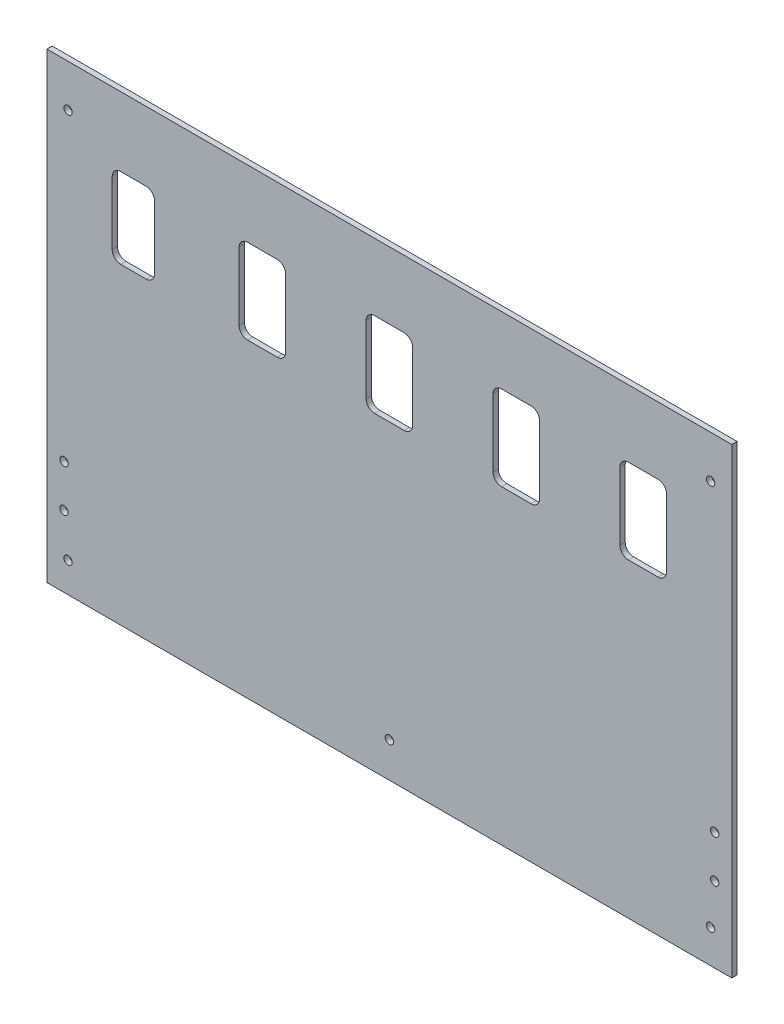
SolidWorks part; units mm, degrees
material "ABS PC"
ref_plane "Front Plane" through (0, 0, 0) normal (0, 0, 1) x (1, 0, 0)
ref_plane "Top Plane" through (0, 0, 0) normal (0, 1, 0) x (1, 0, 0)
ref_plane "Right Plane" through (0, 0, 0) normal (1, 0, 0) x (0, 0, -1)
sketch "Sketch1" plane through (0, 0, 0) normal (0, 0, 1) x (1, 0, 0)
  line L1 (-205.5812, -138.684) -> (205.5812, -138.684)
  line L2 (-205.5812, -138.684) -> (-205.5812, 138.684)
  line L3 (-205.5812, 138.684) -> (205.5812, 138.684)
  line L4 (205.5812, -138.684) -> (205.5812, 138.684)
  line L5 (0, 138.684) -> (0, -138.684) construction
  line L6 (-205.5812, 0) -> (205.5813, 0) construction
  point P0 (0, 0)
  point P4 (-137.0013, 0)
  point P5 (137.0013, 0)
  point P6 (0, 97.0788)
  point P7 (0, -97.0788)
  dimension "Width" = 277.368
  dimension "Break" = 68.58
  dimension "D2" = 68.58
  dimension "D1" = 41.6052
  dimension "D3" = 41.6052
  dimension "D4" = 411.1625
sketch "Sketch2" plane through (0, 0, 0) normal (1, 0, 0) x (0, 0, -1)
  line L0 (-1.5875, -138.684) -> (1.5875, -138.684)
  dimension "Thickness" = 3.175
sketch "Sketch3" plane through (0, 0, 0) normal (0, 0, 1) x (1, 0, 0)
  line L0 (-205.5812, -138.684) -> (-205.5812, 138.684) construction
  line L1 (-205.5812, -138.684) -> (205.5812, -138.684) construction
  line L2 (205.5812, -138.684) -> (205.5812, 138.684) construction
  line L3 (-205.5812, 138.684) -> (205.5812, 138.684) construction
  line L4 (-205.5812, -138.684) -> (-205.5812, 138.684)
  line L5 (-205.5812, -138.684) -> (205.5812, -138.684)
  line L6 (205.5812, -138.684) -> (205.5812, 138.684)
  line L7 (-205.5812, 138.684) -> (205.5812, 138.684)
extrude "Boss-Extrude1" add sketch "Sketch3" along normal mid plane 3.175
sketch "Sketch4" plane through (0, 0, 1.5875) normal (0, 0, 1) x (1, 0, 0)
  line L0 (-227.6475, 73.0327) -> (-161.29, 73.0327) construction
  line L1 (-82.55, 73.0327) -> (-82.55, 98.4327) construction
  line L2 (-82.55, 98.4327) -> (-90.17, 98.4327) construction
  line L3 (-161.29, 73.0327) -> (-161.29, 97.1627) construction
  line L6 (-227.6475, -105.791) -> (-227.6475, 52.959) construction
  line L7 (-227.6475, -115.316) -> (-227.6475, 138.684) construction
  line L8 (-161.29, 73.0327) -> (-82.55, 73.0327) construction
  line L9 (-82.55, 73.0327) -> (-6.35, 73.0327) construction
  line L10 (-6.35, 73.0327) -> (69.85, 73.0327) construction
  line L11 (69.85, 73.0327) -> (146.05, 73.0327) construction
  line L12 (-82.55, 73.0327) -> (-82.55, 47.6327) construction
  line L13 (-82.55, 47.6327) -> (-62.23, 47.6327) construction
  line L16 (-161.29, 97.1627) -> (-166.37, 97.1627) construction
  line L17 (-161.29, 73.0327) -> (-161.29, 48.9027) construction
  line L18 (-161.29, 48.9027) -> (-140.97, 48.9027) construction
  line L19 (-6.35, 73.0327) -> (-6.35, 98.4327) construction
  line L24 (-6.35, 98.4327) -> (-13.97, 98.4327) construction
  line L25 (-6.35, 73.0327) -> (-6.35, 47.6327) construction
  line L26 (-6.35, 47.6327) -> (13.97, 47.6327) construction
  line L27 (69.85, 73.0327) -> (69.85, 98.4327) construction
  line L28 (-8.89, 98.4327) -> (8.89, 98.4327)
  line L29 (-13.97, 93.3527) -> (-13.97, 52.7127)
  line L30 (-8.89, 47.6327) -> (8.89, 47.6327)
  line L31 (13.97, 93.3527) -> (13.97, 52.7127)
  line L32 (69.85, 98.4327) -> (62.23, 98.4327) construction
  line L33 (69.85, 73.0327) -> (69.85, 47.6327) construction
  line L34 (69.85, 47.6327) -> (90.17, 47.6327) construction
  line L35 (146.05, 73.0327) -> (146.05, 98.4327) construction
  line L36 (67.31, 98.4327) -> (85.09, 98.4327)
  line L37 (62.23, 93.3527) -> (62.23, 52.7127)
  line L38 (67.31, 47.6327) -> (85.09, 47.6327)
  line L39 (90.17, 93.3527) -> (90.17, 52.7127)
  line L40 (146.05, 98.4327) -> (138.43, 98.4327) construction
  line L41 (146.05, 73.0327) -> (146.05, 47.6327) construction
  line L42 (146.05, 47.6327) -> (166.37, 47.6327) construction
  line L43 (-205.5812, 138.684) -> (-205.5812, 73.0327) construction
  line L44 (143.51, 98.4327) -> (161.29, 98.4327)
  line L45 (138.43, 93.3527) -> (138.43, 52.7127)
  line L46 (143.51, 47.6327) -> (161.29, 47.6327)
  line L47 (166.37, 93.3527) -> (166.37, 52.7127)
  line L48 (-85.09, 98.4327) -> (-67.31, 98.4327)
  line L49 (-90.17, 93.3527) -> (-90.17, 52.7127)
  line L50 (-85.09, 47.6327) -> (-67.31, 47.6327)
  line L51 (-62.23, 93.3527) -> (-62.23, 52.7127)
  line L53 (-161.29, 97.1627) -> (-146.05, 97.1627)
  line L54 (-166.37, 92.0827) -> (-166.37, 53.9827)
  line L55 (-161.29, 48.9027) -> (-146.05, 48.9027)
  line L56 (-140.97, 92.0827) -> (-140.97, 53.9827)
  arc A0 (138.43, 52.7127) -> (143.51, 47.6327) centre (143.51, 52.7127) ccw
  arc A1 (166.37, 52.7127) -> (161.29, 47.6327) centre (161.29, 52.7127) cw
  arc A2 (161.29, 98.4327) -> (166.37, 93.3527) centre (161.29, 93.3527) cw
  arc A3 (138.43, 93.3527) -> (143.51, 98.4327) centre (143.51, 93.3527) cw
  arc A4 (62.23, 52.7127) -> (67.31, 47.6327) centre (67.31, 52.7127) ccw
  arc A5 (90.17, 52.7127) -> (85.09, 47.6327) centre (85.09, 52.7127) cw
  arc A6 (85.09, 98.4327) -> (90.17, 93.3527) centre (85.09, 93.3527) cw
  arc A7 (67.31, 98.4327) -> (62.23, 93.3527) centre (67.31, 93.3527) ccw
  arc A8 (-13.97, 52.7127) -> (-8.89, 47.6327) centre (-8.89, 52.7127) ccw
  arc A9 (13.97, 52.7127) -> (8.89, 47.6327) centre (8.89, 52.7127) cw
  arc A10 (8.89, 98.4327) -> (13.97, 93.3527) centre (8.89, 93.3527) cw
  arc A11 (-8.89, 98.4327) -> (-13.97, 93.3527) centre (-8.89, 93.3527) ccw
  arc A19 (-90.17, 52.7127) -> (-85.09, 47.6327) centre (-85.09, 52.7127) ccw
  arc A20 (-62.23, 52.7127) -> (-67.31, 47.6327) centre (-67.31, 52.7127) cw
  arc A21 (-67.31, 98.4327) -> (-62.23, 93.3527) centre (-67.31, 93.3527) cw
  arc A22 (-85.09, 98.4327) -> (-90.17, 93.3527) centre (-85.09, 93.3527) ccw
  arc A23 (-166.37, 53.9827) -> (-161.29, 48.9027) centre (-161.29, 53.9827) ccw
  arc A24 (-146.05, 48.9027) -> (-140.97, 53.9827) centre (-146.05, 53.9827) ccw
  arc A25 (-146.05, 97.1627) -> (-140.97, 92.0827) centre (-146.05, 92.0827) cw
  arc A26 (-161.29, 97.1627) -> (-166.37, 92.0827) centre (-161.29, 92.0827) ccw
  point P16 (-76.2, 98.4327)
  point P17 (-90.17, 73.0327)
  point P18 (-13.97, 73.0327)
  point P95 (62.23, 73.0327)
  point P96 (138.43, 73.0327)
  point P97 (0, 98.4327)
  point P98 (76.2, 98.4327)
  point P99 (152.4, 98.4327)
  dimension "D1" = 5.08
  dimension "D2" = 5.08
  dimension "D5" = 5.08
  dimension "D9" = 27.94
  dimension "D10" = 27.94
  dimension "D11" = 27.94
  dimension "D12" = 27.94
  dimension "D3" = 76.2
  dimension "D4" = 76.2
  dimension "D6" = 152.4
  dimension "D7" = 65.6513
extrude "Cut-Extrude1" cut sketch "Sketch4" against normal blind 25.4 contours L53 A26 L54 A23 L55 A24 L56 A25 | A22 L48 A21 L51 A20 L50 A19 L49 | L29 A8 L30 A9 L31 A10 L28 A11 | L37 A4 L38 A5 L39 A6 L36 A7 | A3 L44 A2 L47 A1 L46 A0 L45 region at (-153.67, 73.0327, 1.5875)
hole_wizard "#10 Clearance Hole1" positions "Sketch5" profile "Sketch6" hole size "#10" standard "ANSI Inch" end condition through all
sketch "Sketch5" plane through (0, 0, 1.5875) normal (0, 0, 1) x (1, 0, 0)
  point P6 (192.8812, 113.284)
  point P8 (-192.8812, -120.7642)
  point P10 (192.8812, -118.6475)
  point P12 (-192.8812, 113.284)
sketch "Sketch6" plane through (192.8812, 113.284, 1.5875) normal (1, 0, 0) x (0, -1, 0)
  line L0 (0, 0) -> (0, 3.175)
  line L1 (0, 3.175) -> (2.4892, 3.175)
  line L2 (2.4892, 3.175) -> (2.4892, 0)
  line L5 (2.4892, 0) -> (0, 0)
  line L11 (0, -6.35) -> (0, 107.95) construction
  dimension "Thru Hole Dia." = 4.9784
  dimension "Thru Hole Depth" = 3.175
hole_wizard "#10 Clearance Hole2" positions "Sketch7" profile "Sketch8" hole size "#10" standard "ANSI Inch" end condition through all
sketch "Sketch7" plane through (0, 0, 1.5875) normal (0, 0, 1) x (1, 0, 0)
  point P0 (0, -117.5325)
sketch "Sketch8" plane through (0, -117.5325, 1.5875) normal (1, 0, 0) x (0, -1, 0)
  line L0 (0, 0) -> (0, 3.175)
  line L1 (0, 3.175) -> (2.4892, 3.175)
  line L2 (2.4892, 3.175) -> (2.4892, 0)
  line L5 (2.4892, 0) -> (0, 0)
  line L11 (0, -6.35) -> (0, 107.95) construction
  dimension "Thru Hole Dia." = 4.9784
  dimension "Thru Hole Depth" = 3.175
hole_wizard "#10 Clearance Hole3" positions "Sketch9" profile "Sketch10" hole size "#10" standard "ANSI Inch" end condition through all
sketch "Sketch9" plane through (0, 0, 1.5875) normal (0, 0, 1) x (1, 0, 0)
  point P0 (-195.3063, -70.6157)
sketch "Sketch10" plane through (-195.3063, -70.6157, 1.5875) normal (1, 0, 0) x (0, -1, 0)
  line L0 (0, 0) -> (0, 3.175)
  line L1 (0, 3.175) -> (2.4892, 3.175)
  line L2 (2.4892, 3.175) -> (2.4892, 0)
  line L5 (2.4892, 0) -> (0, 0)
  line L11 (0, -6.35) -> (0, 107.95) construction
  dimension "Thru Hole Dia." = 4.9784
  dimension "Thru Hole Depth" = 3.175
hole_wizard "#10 Clearance Hole4" positions "Sketch11" profile "Sketch12" hole size "#10" standard "ANSI Inch" end condition through all
sketch "Sketch11" plane through (0, 0, 1.5875) normal (0, 0, 1) x (1, 0, 0)
  point P1 (-195.3063, -96.0157)
  point P3 (-195.3063, -96.0157)
sketch "Sketch12" plane through (-195.3063, -96.0157, 1.5875) normal (1, 0, 0) x (0, -1, 0)
  line L0 (0, 0) -> (0, 3.175)
  line L1 (0, 3.175) -> (2.4892, 3.175)
  line L2 (2.4892, 3.175) -> (2.4892, 0)
  line L5 (2.4892, 0) -> (0, 0)
  line L11 (0, -6.35) -> (0, 107.95) construction
  dimension "Thru Hole Dia." = 4.9784
  dimension "Thru Hole Depth" = 3.175
hole_wizard "#10 Clearance Hole5" positions "Sketch13" profile "Sketch14" hole size "#10" standard "ANSI Inch" end condition through all
sketch "Sketch13" plane through (0, 0, 1.5875) normal (0, 0, 1) x (1, 0, 0)
  point P0 (195.3062, -68.0242)
  point P2 (195.3062, -93.4242)
sketch "Sketch14" plane through (195.3062, -68.0242, 1.5875) normal (1, 0, 0) x (0, -1, 0)
  line L0 (0, 0) -> (0, 3.175)
  line L1 (0, 3.175) -> (2.4892, 3.175)
  line L2 (2.4892, 3.175) -> (2.4892, 0)
  line L5 (2.4892, 0) -> (0, 0)
  line L11 (0, -6.35) -> (0, 107.95) construction
  dimension "Thru Hole Dia." = 4.9784
  dimension "Thru Hole Depth" = 3.175
equation "\"D1@Boss-Extrude1\" = \"Thickness@Sketch2\""
equation "\"D2@Sketch1\" = \"Break@Sketch1\""
equation "\"D1@Sketch1\"=\"Width@Sketch1\"*0.15"
equation "\"D3@Sketch1\"=\"D1@Sketch1\""
equation "\"SlotWidth\"= 1.1in"
equation "\"D9@Sketch4\"=\"SlotWidth\""
equation "\"D10@Sketch4\"=\"SlotWidth\""
equation "\"D11@Sketch4\"=\"SlotWidth\""
equation "\"D12@Sketch4\"=\"SlotWidth\""
